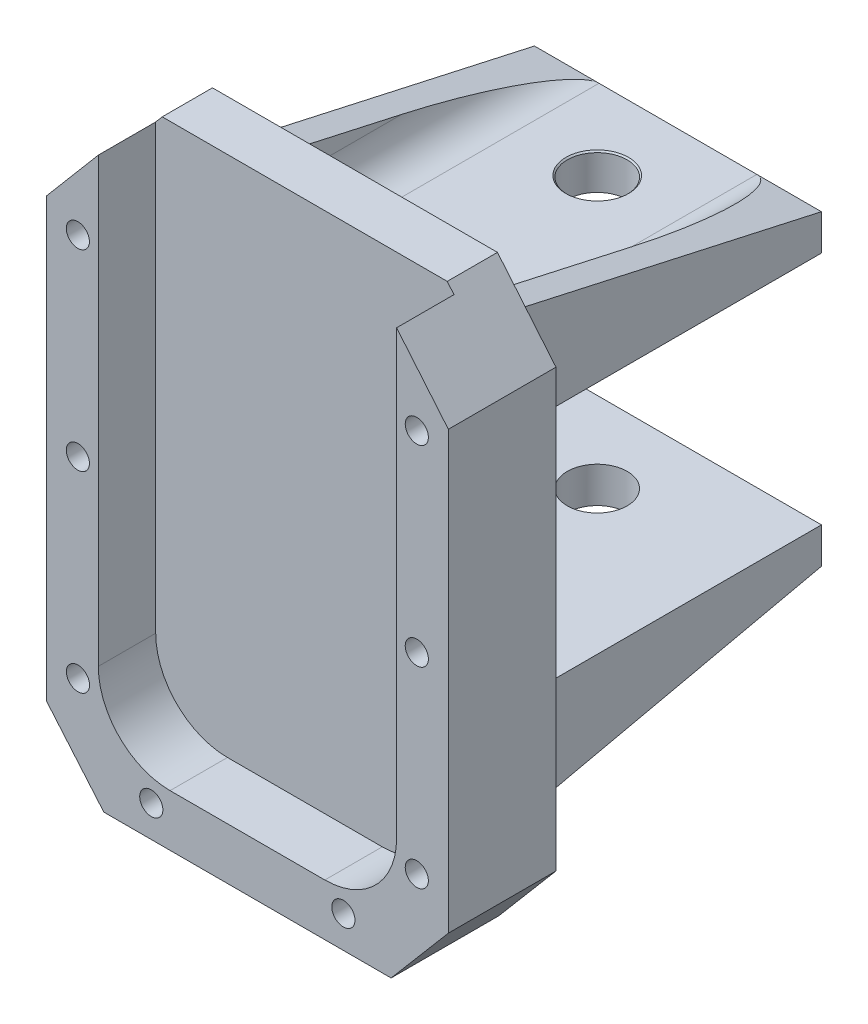
SolidWorks part; units mm, degrees
material "PLA"
ref_plane "Front Plane" through (0, 0, 0) normal (0, 0, 1) x (1, 0, 0)
ref_plane "Top Plane" through (0, 0, 0) normal (0, 1, 0) x (1, 0, 0)
ref_plane "Right Plane" through (0, 0, 0) normal (1, 0, 0) x (0, 0, -1)
sketch "Sketch1" plane through (0, 0, 0) normal (0, 0, 1) x (1, 0, 0)
  line L1 (0, 0) -> (-35.56, 0)
  line L2 (0, 0) -> (0, 50.8)
  line L3 (0, 50.8) -> (-35.56, 50.8)
  line L4 (-35.56, 0) -> (-35.56, 50.8)
  dimension "D1" = 50.8
  dimension "D2" = 35.56
extrude "Boss-Extrude1" add sketch "Sketch1" along normal blind 9.525
sketch "Sketch2" plane through (0, 0, 9.525) normal (0, 0, 1) x (1, 0, 0)
  line L0 (0, 50.8) -> (-35.56, 50.8) construction
  line L1 (-30.98, 50.8) -> (-4.58, 50.8)
  line L2 (-30.98, 50.8) -> (-30.98, 4.58)
  line L3 (-30.98, 4.58) -> (-4.58, 4.58)
  line L4 (-4.58, 50.8) -> (-4.58, 4.58)
  line L5 (-35.56, 0) -> (0, 0) construction
  line L6 (-17.78, 0) -> (-17.78, 4.58) construction
  dimension "D1" = 46.22
  dimension "D2" = 26.4
extrude "Cut-Extrude2" cut sketch "Sketch2" against normal blind 5.08
hole_wizard "Tap Drill for M2.5x0.45 Tap1" positions "Sketch6" profile "Sketch5" hole size "M2.5x0.45" standard "ANSI Metric" end condition through all
sketch "Sketch6" plane through (0, 0, 0) normal (0, 0, -1) x (-1, 0, 0)
  point P0 (2.7924, 43.0871)
  point P2 (2.7924, 26.093)
  point P4 (2.7924, 9.1052)
  point P6 (9.2907, 2.8227)
  point P8 (26.2924, 2.7871)
  point P10 (32.78, 9.1052)
  point P12 (32.7924, 26.0871)
  point P14 (32.7924, 43.0871)
sketch "Sketch5" plane through (-2.7924, 43.0871, 0) normal (1, 0, 0) x (0, 1, 0)
  line L0 (0, 0) -> (0, 9.525)
  line L1 (0, 9.525) -> (1.025, 9.525)
  line L2 (1.025, 9.525) -> (1.025, 0)
  line L5 (1.025, 0) -> (0, 0)
  line L11 (0, -6.35) -> (0, 107.95) construction
  dimension "Thru Hole Dia." = 2.05
  dimension "Thru Hole Depth" = 9.525
sketch "Sketch13" plane through (0, 0, 0) normal (0, 0, -1) x (-1, 0, 0)
  line L0 (35.56, 0) -> (0, 0) construction
  line L1 (30.48, 39.679) -> (5.08, 39.679)
  line L2 (30.48, 39.679) -> (30.48, 36.504)
  line L3 (30.48, 36.504) -> (5.08, 36.504)
  line L4 (5.08, 39.679) -> (5.08, 36.504)
  line L5 (30.48, 39.679) -> (5.08, 36.504) construction
  line L6 (30.48, 36.504) -> (5.08, 39.679) construction
  line L7 (30.48, 15.676) -> (5.08, 15.676)
  line L8 (30.48, 15.676) -> (30.48, 12.501)
  line L9 (30.48, 12.501) -> (5.08, 12.501)
  line L10 (5.08, 15.676) -> (5.08, 12.501)
  line L11 (30.48, 15.676) -> (5.08, 12.501) construction
  line L12 (30.48, 12.501) -> (5.08, 15.676) construction
  line L13 (17.78, 15.676) -> (17.78, 36.504) construction
  line L15 (0, 50.8) -> (35.56, 50.8) construction
  point P0 (17.78, 38.0915)
  point P5 (17.78, 14.0885)
  point P12 (17.78, 0)
  point P15 (17.78, 26.09)
  dimension "D1" = 3.175
  dimension "D2" = 3.175
  dimension "D3" = 25.4
  dimension "D4" = 20.828
  dimension "D5" = 24.71
extrude "Boss-Extrude2" add sketch "Sketch13" along normal blind 28.575
sketch "Sketch8" plane through (0, 0, 9.525) normal (0, 0, 1) x (1, 0, 0)
  line L0 (-5.179, 50.8) -> (0, 44.5915)
  line L1 (-4.58, 50.8) -> (-30.98, 50.8) construction
  line L2 (0, 0) -> (0, 50.8) construction
  line L3 (0.0027, 44.5883) -> (-5.0973, 50.5883) construction
  line L4 (0, 44.5915) -> (0, 50.8)
  line L5 (0, 50.8) -> (-5.179, 50.8)
  line L6 (-35.56, 44.7066) -> (-35.56, 50.8)
  line L7 (-35.56, 50.8) -> (-35.56, 0) construction
  line L8 (-35.56, 50.8) -> (-30.4026, 50.8)
  line L9 (-30.4026, 50.8) -> (-35.56, 44.7066)
  line L10 (-35.56, 5.97) -> (-35.56, 0)
  line L11 (-35.56, 0) -> (-30.4926, 0)
  line L12 (-35.56, 0) -> (0, 0) construction
  line L13 (-30.4926, 0) -> (-35.56, 5.97)
  line L14 (-5.0926, -0.0313) -> (0, 0)
  line L15 (0, 0) -> (0, 5.97)
  line L16 (0, 5.97) -> (-5.0926, -0.0313)
extrude "Cut-Extrude3" cut sketch "Sketch8" against normal through all
ref_plane "Plane6" through (-23.56, 0, 0) normal (-1, 0, 0) x (0, 0, 1)
fillet "Fillet1" radius 6.35 2 edges at (-4.58, 4.58, 6.985) (-30.98, 4.58, 6.985)
sketch "Sketch10" plane through (-43.87, 39.679, 0) normal (0, -1, 0) x (0, 0, -1)
  line L2 (14.2875, 13.39) -> (14.2875, 38.79) construction
  line L3 (0, 38.79) -> (0, 13.39) construction
  line L4 (14.2875, 26.09) -> (0, 26.09) construction
  line L6 (28.575, 13.39) -> (0, 13.39) construction
  line L7 (28.575, 38.79) -> (0, 38.79) construction
  line L8 (14.2875, 26.09) -> (28.575, 26.09) construction
  line L9 (28.575, 38.79) -> (28.575, 13.39) construction
  circle A0 centre (21.4312, 26.09) radius 3.175
  circle A1 centre (7.1438, 26.09) radius 3.175
  dimension "D1" = 6.35
hole_wizard "M5 Clearance Hole1" positions "3DSketch1" profile "Sketch11" hole size "M5" standard "ANSI Metric" end condition through all
sketch3d "3DSketch1"
  point P0 (-17.78, 39.679, -7.1438)
  point P3 (-17.78, 39.679, -21.4312)
sketch "Sketch11" plane through (-17.78, 39.679, -7.1438) normal (1, 0, 0) x (0, 0, 1)
  line L0 (0, 0) -> (0, 39.679)
  line L1 (0, 39.679) -> (2.65, 39.679)
  line L2 (2.65, 39.679) -> (2.65, 0.125)
  line L3 (2.65, 0.125) -> (2.775, 0)
  line L5 (2.775, 0) -> (0, 0)
  line L6 (-2.65, 0.125) -> (-2.775, 0) construction
  line L11 (0, -6.35) -> (0, 107.95) construction
  dimension "Thru Hole Dia." = 5.3
  dimension "Thru Hole Depth" = 39.679
  dimension "Near C'Sink Dia." = 5.55
  dimension "Near C'Sink Angle" = 90
sketch "Sketch14" plane through (-30.48, 0, 0) normal (-1, 0, 0) x (0, 0, 1)
  line L0 (-28.575, 12.501) -> (0, 6.151)
  line L1 (0, 44.7066) -> (0, 5.97) construction
  line L2 (-28.575, 12.501) -> (0, 12.501) construction
  dimension "D1" = 6.35
rib "Rib7" sketch "Sketch14" sketch "Sketch14" thickness 2.54 extrusion direction parallel to sketch draft on no parameters "D1"=2.54
sketch "Sketch15" plane through (-5.08, 0, 0) normal (1, 0, 0) x (0, 0, -1)
  line L0 (28.575, 12.501) -> (0, 6.151)
rib "Rib8" sketch "Sketch15" sketch "Sketch15" thickness 2.54 extrusion direction parallel to sketch draft on no parameters "D1"=2.54
sketch "Sketch16" plane through (-30.48, 0, 0) normal (-1, 0, 0) x (0, 0, 1)
  line L0 (-28.575, 39.679) -> (0, 46.029)
  line L1 (0, 44.7066) -> (0, 5.97) construction
  dimension "D1" = 6.35
sketch "Sketch17" plane through (-5.08, 0, 0) normal (1, 0, 0) x (0, 0, -1)
  line L0 (28.575, 39.679) -> (0, 46.029)
rib "Rib9" sketch "Sketch17" sketch "Sketch17" thickness 2.54 extrusion direction parallel to sketch draft on no parameters "D1"=2.54
rib "Rib10" sketch "Sketch16" sketch "Sketch16" thickness 2.54 extrusion direction parallel to sketch draft on no parameters "D1"=2.54
fillet "Fillet2" radius 3.175 2 edges at (-27.94, 12.501, -14.2875) (-7.62, 12.501, -14.2875)
fillet "Fillet3" radius 3.175 2 edges at (-7.62, 39.679, -14.2875) (-27.94, 39.679, -14.2875)
sketch "Sketch18" plane through (0, 39.679, 0) normal (0, 1, 0) x (1, 0, 0)
  line L0 (-17.78, 7.1438) -> (-17.78, 21.4312) construction
